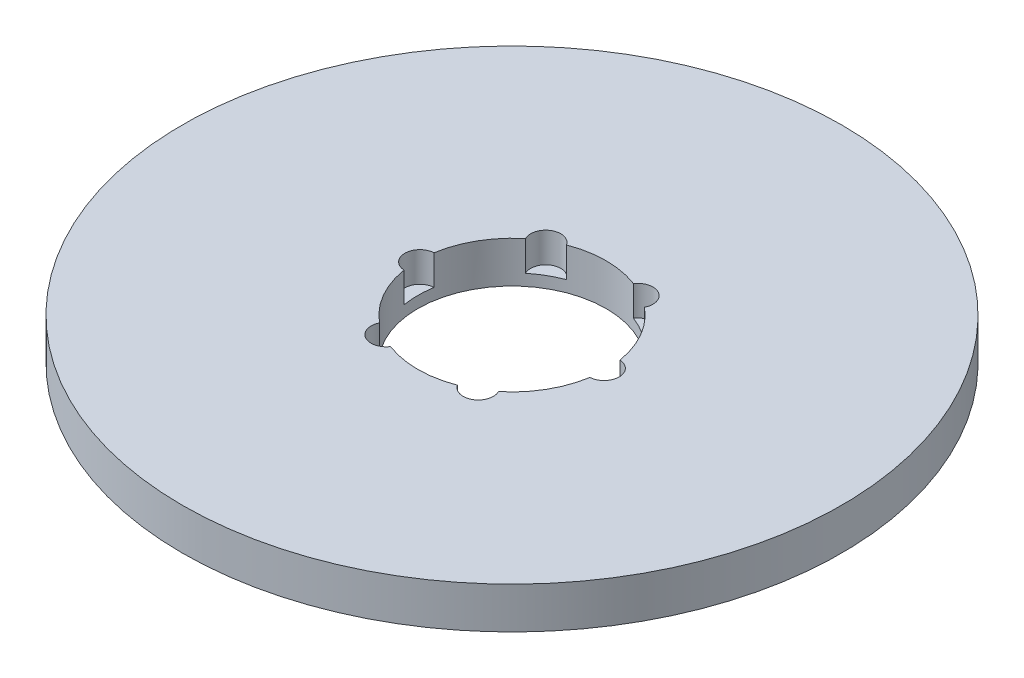
SolidWorks part; units mm, degrees
ref_plane "Front Plane" through (0, 0, 0) normal (0, 0, 1) x (1, 0, 0)
ref_plane "Top Plane" through (0, 0, 0) normal (0, 1, 0) x (1, 0, 0)
ref_plane "Right Plane" through (0, 0, 0) normal (1, 0, 0) x (0, 0, -1)
sketch "Sketch1" plane through (0, 0, 0) normal (0, 1, 0) x (1, 0, 0)
  circle A0 centre (0, 0) radius 87.5
  dimension "FLANGE_OD" = 175
extrude "Boss-Extrude1" add sketch "Sketch1" along normal blind 11
sketch "Sketch2" plane through (0, 0, 0) normal (0, 1, 0) x (1, 0, 0)
  circle A0 centre (0, 0) radius 25
  dimension "BORE_D" = 50
extrude "Cut-Extrude1" cut sketch "Sketch2" along normal through all
sketch "Sketch3" plane through (0, 11, 0) normal (0, 1, 0) x (1, 0, 0)
  circle A0 centre (0, 0) radius 24.465 construction
  circle A1 centre (-24.465, 0) radius 3.9895
  dimension "BOLT_D" = 7.9791
  dimension "BOLT_PCD" = 48.9299
extrude "Cut-Extrude2" cut sketch "Sketch3" against normal blind 7.9693
pattern_circular "CirPattern1" count 6 over 360 about axis through (0, 0, 0) along (0, 1, 0) of "Cut-Extrude2"
